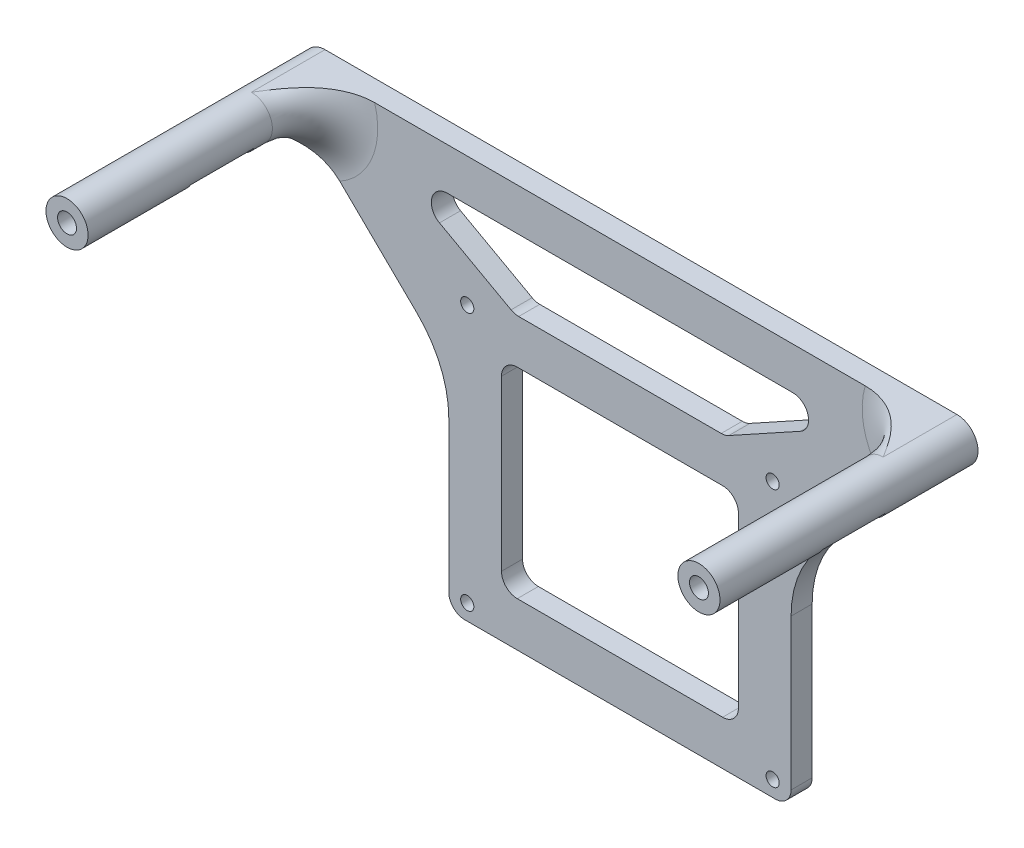
SolidWorks part; units mm, degrees
material "ABS"
ref_plane "Front Plane" through (0, 0, 0) normal (0, 0, 1) x (1, 0, 0)
ref_plane "Top Plane" through (0, 0, 0) normal (0, 1, 0) x (1, 0, 0)
ref_plane "Right Plane" through (0, 0, 0) normal (1, 0, 0) x (0, 0, -1)
sketch "Sketch1" plane through (0, 0, 0) normal (0, 0, 1) x (1, 0, 0)
  line L0 (44.4694, 41) -> (20, 27.5)
  line L1 (32.5, -27.5) -> (-32.5, -27.5)
  line L2 (32.5, -27.5) -> (32.5, 12.5)
  line L3 (20, 27.5) -> (-20, 27.5)
  line L4 (-32.5, -27.5) -> (-32.5, 12.5)
  line L5 (32.5, -27.5) -> (-32.5, 27.5) construction
  line L6 (32.5, 27.5) -> (-32.5, -27.5) construction
  line L7 (-62.7973, 42.1408) -> (-32.5, 12.5)
  line L8 (-44.4694, 41) -> (-20, 27.5)
  line L9 (0, 0) -> (0, 27.5) construction
  line L10 (62.7973, 42.1408) -> (32.5, 12.5)
  line L11 (0, 0) -> (35, 0) construction
  line L12 (-60, 49) -> (60, 49)
  line L13 (-44.4694, 41) -> (44.4694, 41)
  line L14 (-58.0677, 48.5023) -> (-44.4694, 41) construction
  line L15 (58.0677, 48.5023) -> (44.4694, 41) construction
  line L16 (32.5, 12.5) -> (32.5, 27.5) construction
  line L17 (-32.5, 12.5) -> (-32.5, 27.5) construction
  line L18 (-20, 27.5) -> (-32.5, 27.5) construction
  line L19 (32.5, 27.5) -> (20, 27.5) construction
  line L21 (22.5, -19.0385) -> (-22.5, -19.0385)
  line L22 (22.5, -19.0385) -> (22.5, 19.0385)
  line L23 (22.5, 19.0385) -> (-22.5, 19.0385)
  line L24 (-22.5, -19.0385) -> (-22.5, 19.0385)
  line L25 (22.5, -19.0385) -> (-22.5, 19.0385) construction
  line L26 (22.5, 19.0385) -> (-22.5, -19.0385) construction
  arc A0 (-60, 49) -> (-62.7973, 42.1408) centre (-60, 45) ccw
  arc A2 (60, 49) -> (62.7973, 42.1408) centre (60, 45) cw
  arc A3 (62.7973, 42.1408) -> (58.0677, 48.5023) centre (60, 45) cw construction
  arc A4 (-62.7973, 42.1408) -> (-58.0677, 48.5023) centre (-60, 45) ccw construction
  arc A5 (-58.0677, 48.5023) -> (-60, 49) centre (-60, 45) ccw construction
  arc A6 (58.0677, 48.5023) -> (60, 49) centre (60, 45) cw construction
  point P0 (0, 0)
  dimension "D6" = 8
  dimension "D1" = 55
  dimension "D2" = 65
  dimension "D3" = 120
  dimension "D4" = 40
  dimension "D5" = 45
  dimension "D7" = 40
  dimension "D8" = 8
  dimension "D9" = 45
extrude "Boss-Extrude1" add sketch "Sketch1" along normal blind 4 contours L1 L4 | L2 L1 | A2 L12 A0 L7 L4 L1 L2 L10 L8 L13 L0 L3 region at (0, 19.1769, 0)
sketch "Sketch2" plane through (0, 0, 4) normal (0, 0, 1) x (1, 0, 0)
  circle A0 centre (-60, 45) radius 4
  circle A2 centre (60, 45) radius 4
  arc A4 (-60, 49) -> (-62.7973, 42.1408) centre (-60, 45) ccw construction
  arc A5 (62.7973, 42.1408) -> (60, 49) centre (60, 45) ccw construction
extrude "Boss-Extrude2" add sketch "Sketch2" along normal blind 45
hole_wizard "Tap Drill for M3 Tap1" positions "Sketch3" profile "Sketch4" hole size "M3" standard "DIN" end condition up to next
sketch "Sketch3" plane through (0, 0, 0) normal (0, 0, -1) x (-1, 0, 0)
  line L0 (0, 0) -> (0, 49) construction
  line L3 (0, 0) -> (-32.5, 0) construction
  line L7 (60, 49) -> (-60, 49) construction
  line L8 (-32.5, -27.5) -> (-32.5, 12.5) construction
  point P0 (-29, 24.5)
  point P2 (-29, -24.5)
  point P4 (29, -24.5)
  point P6 (29, 24.5)
  point P25 (0, 0)
  point P26 (0, 0)
  point P27 (-40, 0)
  point P30 (-40, 0)
  point P31 (-40, 0)
  point P32 (0, 0)
  point P33 (0, 62.25)
  point P36 (0, 0)
  point P37 (-35, 0)
  dimension "D1" = 49
  dimension "D2" = 58
sketch "Sketch4" plane through (29, 24.5, 0) normal (1, 0, 0) x (0, 1, 0)
  line L0 (0, 0) -> (0, 4)
  line L1 (0, 4) -> (1.25, 4)
  line L2 (1.25, 4) -> (1.25, 0)
  line L5 (1.25, 0) -> (0, 0)
  line L11 (0, -6.35) -> (0, 107.95) construction
  dimension "Thru Hole Dia." = 2.5
  dimension "Thru Hole Depth" = 4
sketch "Sketch5" plane through (0, 0, 49) normal (0, 0, 1) x (1, 0, 0)
  line L0 (-63.4641, 43) -> (-56.5359, 43)
  line L1 (56.5359, 43) -> (63.4641, 43)
  circle A0 centre (60, 45) radius 4 construction
  circle A1 centre (-60, 45) radius 4 construction
  circle A2 centre (60, 45) radius 4
  circle A3 centre (-60, 45) radius 4
  point P10 (-60, 49)
  circle M4 centre (-60, 45) radius 4
  dimension "D1" = 6
extrude "Cut-Extrude1" cut sketch "Sketch5" against normal blind 12 from offset 20 contours L0 M4 | L1 A2 region at (-60, 42.1799, 49) region at (60, 42.1799, 49) offset against normal yes
hole_wizard "CSK for M3 Countersunk Flat Head Screw1" positions "Sketch6" profile "Sketch8" countersink size "M3" standard "DIN" end condition up to next
sketch "Sketch6" plane through (0, 0, 0) normal (0, 0, -1) x (-1, 0, 0)
  point P0 (-60, 45)
  point P3 (60, 45)
sketch "Sketch8" plane through (60, 45, 0) normal (1, 0, 0) x (0, 1, 0)
  line L0 (0, 0) -> (0, 49)
  line L1 (0, 49) -> (1.8, 49)
  line L2 (1.8, 49) -> (1.8, 1.35)
  line L3 (1.8, 1.35) -> (3.15, 0)
  line L5 (3.15, 0) -> (0, 0)
  line L6 (-1.8, 1.35) -> (-3.15, 0) construction
  line L11 (0, -6.35) -> (0, 107.95) construction
  dimension "Thru Hole Dia." = 3.6
  dimension "Thru Hole Depth" = 49
  dimension "Near C'Sink Dia." = 6.3
  dimension "Near C'Sink Angle" = 90
fillet "Fillet1" radius 3 4 edges at (-20, 27.5, 2) (-44.4694, 41, 2) (20, 27.5, 2) (44.4694, 41, 2)
fillet "Fillet2" radius 10 2 edges at (-56.2962, 43.4895, 4) (56.2962, 43.4895, 4)
fillet "Fillet3" radius 20 2 edges at (-32.5, 12.5, 2) (32.5, 12.5, 2)
fillet "Fillet4" radius 3 6 edges at (-32.5, -27.5, 2) (32.5, -27.5, 2) (22.5, -19.0385, 2) (22.5, 19.0385, 2) (-22.5, 19.0385, 2) (-22.5, -19.0385, 2)
